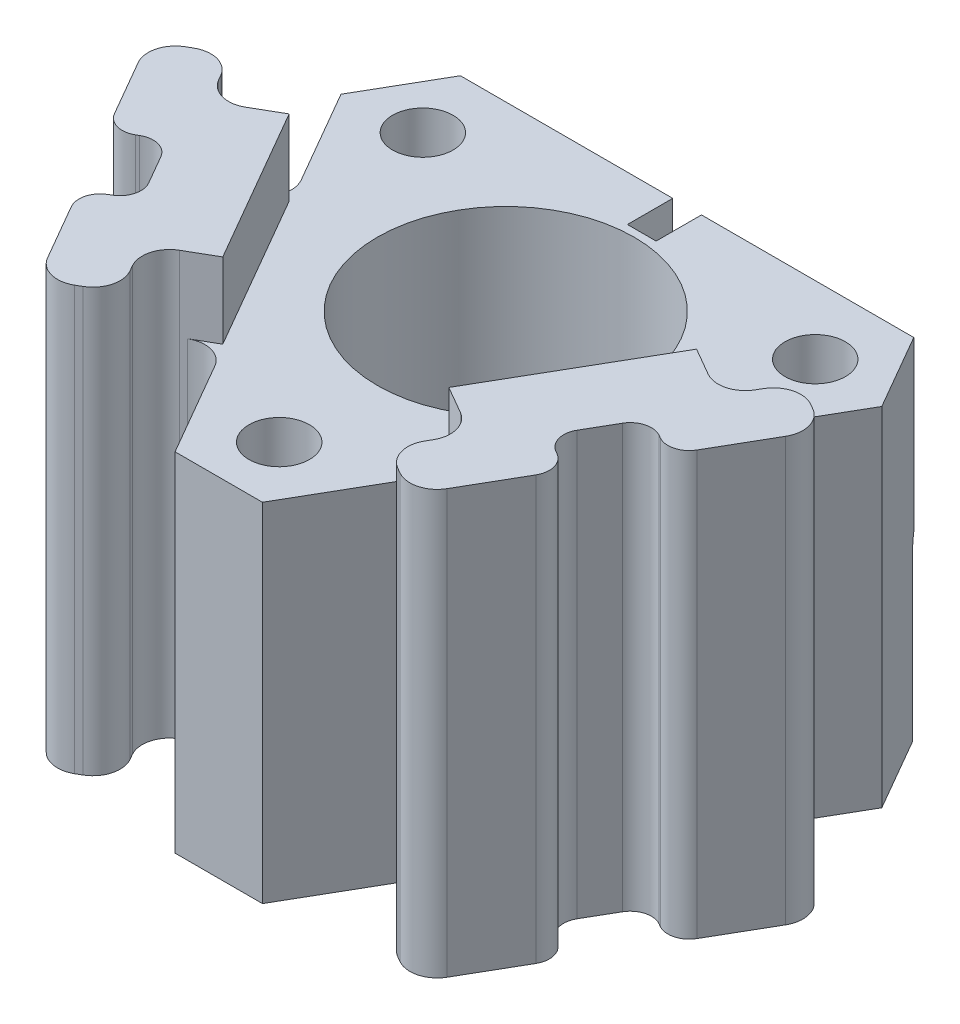
SolidWorks part; units mm, degrees
material "Nylon 101"
ref_plane "Plan de face" through (0, 0, 0) normal (0, 0, 1) x (1, 0, 0)
ref_plane "Plan de dessus" through (0, 0, 0) normal (0, 1, 0) x (1, 0, 0)
ref_plane "Plan de droite" through (0, 0, 0) normal (1, 0, 0) x (0, 0, -1)
sketch "Esquisse2" plane through (0, 0, 0) normal (0, 1, 0) x (1, 0, 0)
  line L5 (0, 0) -> (0, 12) construction
  line L6 (15, 12) -> (-15, 12)
  line L10 (2.8923, -18.9904) -> (17.8923, 6.9904)
  line L11 (0, 0) -> (10.3923, -6) construction
  line L12 (-17.8923, 6.9904) -> (-2.8923, -18.9904)
  line L13 (0, 0) -> (-10.3923, -6) construction
  line L14 (-15, 12) -> (-17.8923, 6.9904)
  line L15 (-2.8923, -18.9904) -> (2.8923, -18.9904)
  line L16 (17.8923, 6.9904) -> (15, 12)
  circle A0 centre (0, 0) radius 6.75 construction
  circle A1 centre (0, 0) radius 8.5
  point P6 (0, 12)
  point P15 (0, 0)
  dimension "D4" = 17
  dimension "D5" = 13.5
  dimension "D1" = 30
  dimension "D2" = 3
  dimension "D3" = 12
extrude "Boss.-Extru.1" add sketch "Esquisse2" along normal blind 23
sketch "Esquisse3" plane through (0, 0, 0) normal (0, 1, 0) x (1, 0, 0)
  line L0 (0, 0) -> (3.3, 0) construction
  line L1 (0, 0) -> (0, 3.3) construction
  line L2 (-16.4462, 9.4952) -> (0, 0) construction
  line L5 (-17.8923, 6.9904) -> (-15, 12) construction
  line L6 (0, 0) -> (16.4462, 9.4952) construction
  line L7 (15, 12) -> (17.8923, 6.9904) construction
  line L8 (0, 0) -> (0, -18.9904) construction
  line L9 (2.8923, -18.9904) -> (-2.8923, -18.9904) construction
  circle A0 centre (0, 0) radius 3.3 construction
  circle A5 centre (-12.9821, 7.4952) radius 2
  circle A7 centre (12.9821, 7.4952) radius 2
  circle A8 centre (0, -14.9904) radius 2
  point P23 (0, 0)
  dimension "D1" = 6.6
  dimension "D3" = 4
  dimension "D2" = 4
  dimension "D4" = 3
extrude "Enlèv. mat.-Extru.3" cut sketch "Esquisse3" against normal blind 8 and the other way through all from surface starting at face at (0, 23, 0)
sketch "Esquisse4" plane through (0, 0, 0) normal (0, 0, 1) x (1, 0, 0)
  line L0 (0, 0) -> (0, 7) construction
  line L1 (11, 3) -> (-11, 3) construction
  line L2 (11, 3) -> (11, 11) construction
  line L3 (11, 11) -> (-11, 11) construction
  line L4 (-11, 3) -> (-11, 11) construction
  line L5 (11, 3) -> (-11, 11) construction
  line L6 (11, 11) -> (-11, 3) construction
  line L8 (-17.8923, 0) -> (-2.8923, 0) construction
  circle A0 centre (-11, 11) radius 1.5
  circle A1 centre (11, 11) radius 1.5
  circle A2 centre (11, 3) radius 1.5
  circle A3 centre (-11, 3) radius 1.5
  point P0 (0, 7)
  dimension "D4" = 3
  dimension "D1" = 8
  dimension "D2" = 22
  dimension "D3" = 3
extrude "Enlèv. mat.-Extru.4" cut sketch "Esquisse4" along normal blind 8 from surface starting at face at (0, 11.5, -12)
sketch "Esquisse5" plane through (0, 0, 0) normal (0, 1, 0) x (1, 0, 0)
  line L0 (0, 0) -> (0, -18.9904) construction
  line L1 (2.8923, -18.9904) -> (-2.8923, -18.9904) construction
  line L2 (10.3923, -6) -> (17.3205, -10) construction
  line L3 (17.8923, 6.9904) -> (2.8923, -18.9904) construction
  line L4 (13.2205, -17.1014) -> (15.3705, -13.3775)
  line L5 (20.7617, -0.4397) -> (20.4153, -0.2397)
  line L6 (17.9564, -0.8986) -> (17.7564, -1.245)
  line L7 (15.2976, -1.9038) -> (13.3923, -0.8038)
  line L8 (13.3923, -0.8038) -> (7.3923, -11.1962)
  line L9 (9.2976, -12.2962) -> (7.3923, -11.1962)
  line L10 (9.7564, -15.1014) -> (9.9564, -14.755)
  line L11 (10.7617, -17.7603) -> (10.4153, -17.5603)
  line L12 (20.7617, -0.4397) -> (20.4153, -0.2397)
  line L13 (17.9564, -0.8986) -> (17.7564, -1.245)
  line L14 (15.2976, -1.9038) -> (13.3923, -0.8038)
  line L15 (9.2976, -12.2962) -> (7.3923, -11.1962)
  line L16 (9.7564, -15.1014) -> (9.9564, -14.755)
  line L17 (10.7617, -17.7603) -> (10.4153, -17.5603)
  line L18 (-17.3205, -10) -> (-18.5705, -7.8349) construction
  line L19 (-16.0705, -12.1651) -> (-17.3205, -10) construction
  line L20 (-10.3923, -6) -> (-17.3205, -10) construction
  line L21 (-19.2705, -6.6225) -> (-21.4205, -2.8986)
  line L22 (-17.1849, -7.0349) -> (-17.3581, -7.1349)
  line L23 (-14.1724, -9.4526) -> (-15.2724, -7.5474)
  line L24 (-14.8581, -11.4651) -> (-14.6849, -11.3651)
  line L25 (-10.7617, -17.7603) -> (-10.4153, -17.5603)
  line L26 (-9.7564, -15.1014) -> (-9.9564, -14.755)
  line L27 (-9.2976, -12.2962) -> (-7.3923, -11.1962)
  line L28 (-15.2976, -1.9038) -> (-13.3923, -0.8038)
  line L29 (-17.9564, -0.8986) -> (-17.7564, -1.245)
  line L30 (-20.7617, -0.4397) -> (-20.4153, -0.2397)
  line L31 (-10.7617, -17.7603) -> (-10.4153, -17.5603)
  line L32 (-9.7564, -15.1014) -> (-9.9564, -14.755)
  line L33 (14.8581, -11.4651) -> (14.6849, -11.3651)
  line L34 (14.1724, -9.4526) -> (15.2724, -7.5474)
  line L35 (17.1849, -7.0349) -> (17.3581, -7.1349)
  line L36 (16.0705, -12.1651) -> (17.3205, -10) construction
  line L37 (19.2705, -6.6225) -> (21.4205, -2.8986)
  line L38 (17.3205, -10) -> (18.5705, -7.8349) construction
  line L39 (-9.2976, -12.2962) -> (-7.3923, -11.1962)
  line L40 (-13.3923, -0.8038) -> (-7.3923, -11.1962)
  line L41 (-15.2976, -1.9038) -> (-13.3923, -0.8038)
  line L42 (-17.9564, -0.8986) -> (-17.7564, -1.245)
  line L43 (-20.7617, -0.4397) -> (-20.4153, -0.2397)
  line L44 (-13.2205, -17.1014) -> (-15.3705, -13.3775)
  arc A0 (10.7617, -17.7603) -> (13.2205, -17.1014) centre (11.6617, -16.2014) ccw
  arc A1 (9.7564, -15.1014) -> (10.4153, -17.5603) centre (11.3153, -16.0014) ccw
  arc A2 (9.2976, -12.2962) -> (9.9564, -14.755) centre (8.3976, -13.855) cw
  arc A3 (21.4205, -2.8986) -> (20.7617, -0.4397) centre (19.8617, -1.9986) ccw
  arc A4 (17.7564, -1.245) -> (15.2976, -1.9038) centre (16.1976, -0.345) cw
  arc A5 (20.4153, -0.2397) -> (17.9564, -0.8986) centre (19.5153, -1.7986) ccw
  arc A6 (10.4153, -17.5603) -> (9.7564, -15.1014) centre (11.3153, -16.0014) cw
  arc A7 (9.9564, -14.755) -> (9.2976, -12.2962) centre (8.3976, -13.855) ccw
  arc A8 (13.2205, -17.1014) -> (10.7617, -17.7603) centre (11.6617, -16.2014) cw
  arc A9 (15.2976, -1.9038) -> (17.7564, -1.245) centre (16.1976, -0.345) ccw
  arc A10 (17.9564, -0.8986) -> (20.4153, -0.2397) centre (19.5153, -1.7986) cw
  arc A11 (20.7617, -0.4397) -> (21.4205, -2.8986) centre (19.8617, -1.9986) cw
  arc A24 (17.3581, -7.1349) -> (19.2705, -6.6225) centre (18.0581, -5.9225) ccw
  arc A25 (15.2724, -7.5474) -> (17.1849, -7.0349) centre (16.4849, -8.2474) cw
  arc A26 (14.6849, -11.3651) -> (14.1724, -9.4526) centre (15.3849, -10.1526) cw
  arc A27 (14.8581, -11.4651) -> (15.3705, -13.3775) centre (14.1581, -12.6775) cw
  arc A28 (-14.8581, -11.4651) -> (-15.3705, -13.3775) centre (-14.1581, -12.6775) ccw
  arc A29 (-14.6849, -11.3651) -> (-14.1724, -9.4526) centre (-15.3849, -10.1526) ccw
  arc A30 (-15.2724, -7.5474) -> (-17.1849, -7.0349) centre (-16.4849, -8.2474) ccw
  arc A31 (-17.3581, -7.1349) -> (-19.2705, -6.6225) centre (-18.0581, -5.9225) cw
  arc A32 (-20.7617, -0.4397) -> (-21.4205, -2.8986) centre (-19.8617, -1.9986) ccw
  arc A33 (-17.9564, -0.8986) -> (-20.4153, -0.2397) centre (-19.5153, -1.7986) ccw
  arc A34 (-15.2976, -1.9038) -> (-17.7564, -1.245) centre (-16.1976, -0.345) cw
  arc A35 (-13.2205, -17.1014) -> (-10.7617, -17.7603) centre (-11.6617, -16.2014) ccw
  arc A36 (-9.9564, -14.755) -> (-9.2976, -12.2962) centre (-8.3976, -13.855) cw
  arc A37 (-10.4153, -17.5603) -> (-9.7564, -15.1014) centre (-11.3153, -16.0014) ccw
  arc A38 (-20.4153, -0.2397) -> (-17.9564, -0.8986) centre (-19.5153, -1.7986) cw
  arc A39 (-17.7564, -1.245) -> (-15.2976, -1.9038) centre (-16.1976, -0.345) ccw
  arc A40 (-21.4205, -2.8986) -> (-20.7617, -0.4397) centre (-19.8617, -1.9986) cw
  arc A41 (-9.2976, -12.2962) -> (-9.9564, -14.755) centre (-8.3976, -13.855) ccw
  arc A42 (-9.7564, -15.1014) -> (-10.4153, -17.5603) centre (-11.3153, -16.0014) cw
  arc A43 (-10.7617, -17.7603) -> (-13.2205, -17.1014) centre (-11.6617, -16.2014) cw
  point P19 (12.3205, -18.6603)
  point P22 (8.8564, -16.6603)
  point P25 (10.8564, -13.1962)
  point P28 (22.3205, -1.3397)
  point P31 (16.8564, -2.8038)
  point P34 (18.8564, 0.6603)
  point P64 (14.7224, -8.5)
  point P72 (15.9724, -6.3349)
  point P75 (13.4724, -10.6651)
  point P88 (-13.4724, -10.6651)
  point P89 (-15.9724, -6.3349)
  point P90 (-18.8564, 0.6603)
  point P91 (-16.8564, -2.8038)
  point P92 (-22.3205, -1.3397)
  point P93 (-10.8564, -13.1962)
  point P94 (-8.8564, -16.6603)
  point P95 (-12.3205, -18.6603)
  dimension "D5" = 1.8
  dimension "D8" = 1.4
  dimension "D1" = 8
  dimension "D2" = 4
  dimension "D3" = 4
  dimension "D4" = 10
  dimension "D6" = 3
  dimension "D7" = 5
extrude "Boss.-Extru.2" add sketch "Esquisse5" against normal up to surface and the other way blind 5 from surface contours L5 A5 L6 A4 L7 L8 L9 A2 L10 A1 L11 A0 L4 A3 | L25 A37 L26 A36 L27 L40 L28 A34 L29 A33 L30 A32 L21 A31 L22 A30 L23 A29 L24 A28 L44 A35 region at (13.999, 0, 8.0823) region at (-13.999, 0, 8.0823) up to face at (0, 0, 0) starting at face at (-12.9821, 23, -5.4952)
fillet "Congé5" radius 1.8 4 edges at (13.3923, 11.5, 0.8038) (7.3923, 11.5, 11.1962) (-7.3923, 11.5, 11.1962) (-13.3923, 11.5, 0.8038)
sketch "Esquisse6" plane through (0, 0, 0) normal (0, 1, 0) x (1, 0, 0)
  line L0 (-13.3923, -0.8038) -> (-7.3923, -11.1962)
  line L1 (-7.3923, -11.1962) -> (-7.4789, -11.2462)
  line L2 (-7.3923, -11.1962) -> (-9.2976, -12.2962) construction
  line L3 (-7.4789, -11.2462) -> (-13.4789, -0.8538)
  line L4 (-13.3923, -0.8038) -> (-15.2976, -1.9038) construction
  line L5 (-13.4789, -0.8538) -> (-13.3923, -0.8038)
  line L6 (7.3923, -11.1962) -> (13.3923, -0.8038)
  line L7 (13.3923, -0.8038) -> (13.4789, -0.8538)
  line L8 (14.9512, -1.7038) -> (13.3923, -0.8038) construction
  line L9 (13.4789, -0.8538) -> (7.4789, -11.2462)
  line L10 (7.3923, -11.1962) -> (9.2976, -12.2962) construction
  line L11 (7.4789, -11.2462) -> (7.3923, -11.1962)
  dimension "D1" = 0.1
  dimension "D2" = 0.1
extrude "Enlèv. mat.-Extru.5" cut sketch "Esquisse6" along normal up to surface (28 mm away) from surface up to face at (-14.8463, 28, 8.5715) starting at face at (-12.9821, 23, -5.4952)
sketch "Esquisse7" plane through (0, 0, -12) normal (0, 0, -1) x (-1, 0, 0)
  line L0 (15, 23) -> (15, 0) construction
  line L1 (-15, 0) -> (15, 0) construction
  line L2 (-15, 0) -> (-15, 14) construction
  line L3 (-15, 14) -> (-0.85, 14) construction
  line L4 (15, 0) -> (15, 14) construction
  line L5 (-15, 23) -> (15, 23) construction
  line L6 (0.85, 0) -> (-0.85, 0)
  line L7 (0.85, 14) -> (0.85, 23) construction
  line L8 (0.85, 23) -> (-0.85, 23) construction
  line L9 (-0.85, 14) -> (-0.85, 23) construction
  line L10 (-0.85, 0) -> (-0.85, 14) construction
  line L11 (0.85, 0) -> (0.85, 14) construction
  line L12 (-0.85, 14) -> (0.85, 14) construction
  line L13 (0.85, 14) -> (15, 14) construction
  line L14 (-15.1, -0.1) -> (-15.1, 14.1)
  line L15 (-15.1, 14.1) -> (-0.95, 14.1)
  line L16 (-0.95, 14.1) -> (-0.95, 23.1)
  line L17 (0.95, 23.1) -> (-0.95, 23.1)
  line L18 (0.95, 14.1) -> (0.95, 23.1)
  line L19 (0.95, 14.1) -> (15.1, 14.1)
  line L20 (15.1, -0.1) -> (15.1, 14.1)
  line L21 (-15.1, -0.1) -> (15.1, -0.1)
  circle A0 centre (11, 11) radius 1.5 construction
  circle M9 centre (-11, 3) radius 1.5
  circle M10 centre (11, 11) radius 1.5
  circle M11 centre (11, 3) radius 1.5
  circle M12 centre (-11, 11) radius 1.5
  line M13 (-15, 0) -> (15, 0)
  line M14 (15, 0) -> (15, 23)
  line M15 (15, 23) -> (-15, 23)
  line M16 (-15, 23) -> (-15, 0)
  dimension "D1" = 3
  dimension "D2" = 0.85
  dimension "D3" = 0.85
  dimension "D4" = 0.1
extrude "Enlèv. mat.-Extru.6" cut sketch "Esquisse7" against normal blind 3 contours L14 L21 L20 L19 L15 M14 M13 M16 | L19 L18 L16 L15 M15 M16 M13 M14 M10 M12 M11 M9 | L18 L17 L16 M15 region at (-7.925, -0.0334, -12) region at (0, 7.5259, -12) region at (0, 23.05, -12)
fillet "Congé6" radius 3 2 edges at (-15.1, 14.1, -10.4134) (15.1, 14.1, -10.4134)
